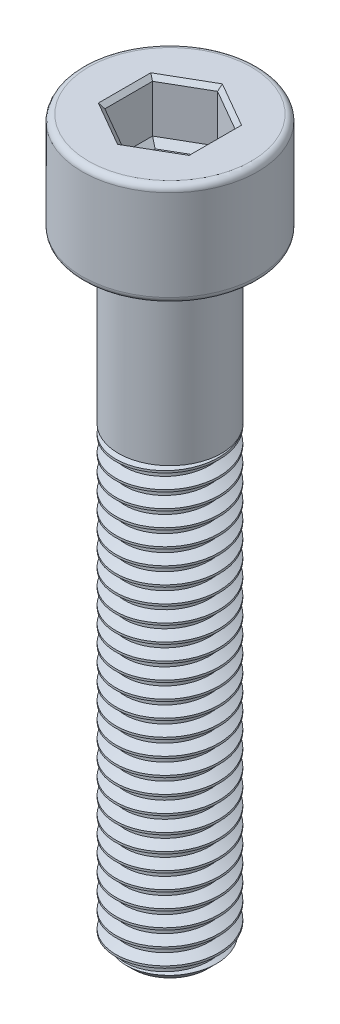
SolidWorks part; units mm, degrees
material "AISI Type A2 Tool Steel"
ref_plane "Front Plane" through (0, 0, 0) normal (0, 0, 1) x (1, 0, 0)
ref_plane "Top Plane" through (0, 0, 0) normal (0, 1, 0) x (1, 0, 0)
ref_plane "Right Plane" through (0, 0, 0) normal (1, 0, 0) x (0, 0, -1)
sketch "Sketch1" plane through (0, 0, 0) normal (0, 1, 0) x (1, 0, 0)
  circle A0 centre (0, 0) radius 2.5
  dimension "D1" = 5
extrude "Boss-Extrude1" add sketch "Sketch1" along normal blind 22
thread "Thread1" pitch 0.8 start angle 0, offset 1, length 0, pitch 0.8, diameter 5
ref_plane "Plane1" through (-2.5, 23, 0) normal (0, 0, 1) x (-1, 0, 0)
sketch "Thread Profile1" plane through (-2.5, 23, 0) normal (0, 0, 1) x (-1, 0, 0)
  line L0 (0, 0) -> (0, 0.8) construction
  line L11 (0, 0) -> (0, 0.7)
  line L12 (0, 0.7) -> (-0.433, 0.45)
  line L13 (-0.433, 0.45) -> (-0.433, 0.25)
  line L15 (-0.433, 0.25) -> (0, 0)
  line L17 (-0.433, 0.35) -> (0, 0.35) construction
  point P2 (0, 0)
  dimension "Pitch" = 0.8
  dimension "Profile_Angle" = 60
  dimension "Profile_Land" = 0.2
  dimension "Profile_Height" = 0.433
sketch "Sketch2" plane through (0, 22, 0) normal (0, 1, 0) x (1, 0, 0)
  circle A0 centre (0, 0) radius 2.5
  dimension "D1" = 5
extrude "Boss-Extrude2" add sketch "Sketch2" along normal blind 8
sketch "Sketch3" plane through (0, 30, 0) normal (0, 1, 0) x (1, 0, 0)
  circle A0 centre (0, 0) radius 4.25
  dimension "D1" = 8.5
extrude "Boss-Extrude3" add sketch "Sketch3" along normal blind 5
fillet "Fillet1" radius 0.3 2 edges at (0, 30, 4.25) (0, 35, 4.25)
sketch "Sketch4" plane through (0, 0, 0) normal (0, 0, 1) x (1, 0, 0)
  line L0 (0, 0) -> (0, 0.4416) construction
  line L1 (0, 0) -> (2.51, 0) construction
  line L2 (2.51, 0) -> (2.51, 0.7)
  line L3 (2.51, 0.7) -> (1.81, 0)
  line L4 (1.81, 0) -> (2.51, 0)
  dimension "D1" = 0.7
  dimension "D2" = 45
  dimension "D3" = 2.51
revolve "Cut-Revolve1" cut sketch "Sketch4" angle 360 about L0
sketch "Sketch5" plane through (0, 35, 0) normal (0, 1, 0) x (1, 0, 0)
  line L1 (0, 2.3094) -> (-2, 1.1547)
  line L2 (-2, 1.1547) -> (-2, -1.1547)
  line L3 (-2, -1.1547) -> (0, -2.3094)
  line L4 (0, -2.3094) -> (2, -1.1547)
  line L5 (2, -1.1547) -> (2, 1.1547)
  line L6 (2, 1.1547) -> (0, 2.3094)
  circle A0 centre (0, 0) radius 2 construction
  dimension "D1" = 4
extrude "Cut-Extrude1" cut sketch "Sketch5" against normal blind 2.5
chamfer "Chamfer1" distance 0.2 angle 45 6 edges at (-1, 35, 1.7321) (1, 35, 1.7321) (2, 35, 0) (1, 35, -1.7321) (-1, 35, -1.7321) (-2, 35, 0)
sketch "Sketch6" plane through (0, 32.5, 0) normal (0, 1, 0) x (1, 0, 0)
  line L1 (0, 2.3094) -> (-2, 1.1547)
  line L2 (-2, 1.1547) -> (-2, -1.1547)
  line L3 (-2, -1.1547) -> (0, -2.3094)
  line L4 (0, -2.3094) -> (2, -1.1547)
  line L5 (2, -1.1547) -> (2, 1.1547)
  line L6 (2, 1.1547) -> (0, 2.3094)
  circle A0 centre (0, 0) radius 2 construction
extrude "Cut-Extrude2" cut sketch "Sketch6" against normal blind 0.3 draft 45
